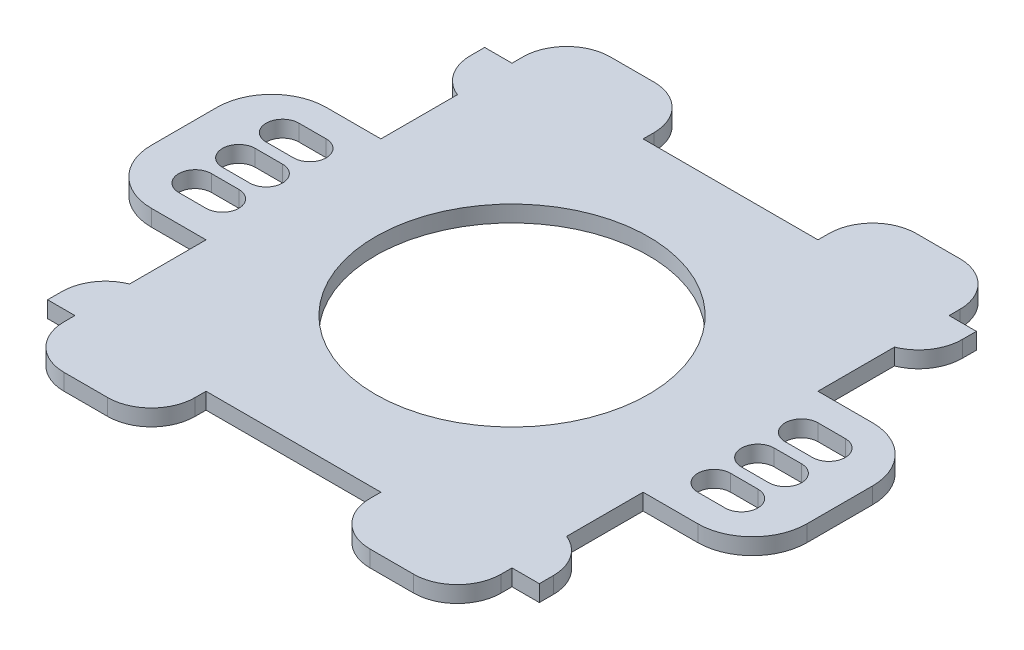
SolidWorks part; units mm, degrees
material "Thornel Mat VMA"
ref_plane "前视基准面" through (0, 0, 0) normal (0, 0, 1) x (1, 0, 0)
ref_plane "上视基准面" through (0, 0, 0) normal (0, 1, 0) x (1, 0, 0)
ref_plane "右视基准面" through (0, 0, 0) normal (1, 0, 0) x (0, 0, -1)
other "Configuration Table"
sketch "草图1" plane through (0, 0, 0) normal (0, 1, 0) x (1, 0, 0)
  line L1 (-20, -25) -> (20, -25)
  line L2 (-20, -25) -> (-20, 25)
  line L3 (-20, 25) -> (20, 25)
  line L4 (20, -25) -> (20, 25)
  line L5 (-20, -25) -> (20, 25) construction
  line L6 (-20, 25) -> (20, -25) construction
  point P0 (0, 0)
  dimension "D1" = 40
  dimension "D2" = 50
extrude "凸台-拉伸1" add sketch "草图1" along normal blind 1.5
sketch "草图3" plane through (0, 1.5, 0) normal (0, 1, 0) x (1, 0, 0)
  line L0 (-1000, 0) -> (49000, 0) construction
  line L1 (-22.5, -20) -> (22.5, -20)
  line L2 (-22.5, -20) -> (-22.5, -15)
  line L3 (-22.5, -15) -> (22.5, -15)
  line L4 (22.5, -20) -> (22.5, -15)
  line L5 (-22.5, -20) -> (22.5, -15) construction
  line L6 (-22.5, -15) -> (22.5, -20) construction
  line L7 (-20, -25) -> (20, -25) construction
  line L8 (-22.5, 15) -> (22.5, 15)
  line L9 (22.5, 20) -> (22.5, 15)
  line L10 (-22.5, 20) -> (22.5, 20)
  line L11 (-22.5, 20) -> (-22.5, 15)
  point P0 (0, -17.5)
  dimension "D1" = 5
  dimension "D2" = 5
  dimension "D3" = 45
  dimension "D4" = 0
extrude "凸台-拉伸2" add sketch "草图3" against normal blind 1.5
sketch "草图4" plane through (0, 1.5, 0) normal (0, 1, 0) x (1, 0, 0)
  line L4 (-30, -8) -> (30, -8)
  line L5 (-30, -8) -> (-30, 8)
  line L6 (-30, 8) -> (30, 8)
  line L7 (30, -8) -> (30, 8)
  line L8 (-30, -8) -> (30, 8) construction
  line L9 (-30, 8) -> (30, -8) construction
  point P0 (0, 0)
  dimension "D4" = 0
  dimension "D1" = 16
  dimension "D2" = 60
  dimension "D3" = 0
extrude "凸台-拉伸3" add sketch "草图4" against normal blind 1.5
sketch "草图6" plane through (0, 1.5, 0) normal (0, 1, 0) x (1, 0, 0)
  line L1 (-25, 0) -> (-22.5, 0) construction
  line L2 (-25, 1.5) -> (-22.5, 1.5)
  line L3 (-25, -1.5) -> (-22.5, -1.5)
  line L4 (-25, 4) -> (-22.5, 4) construction
  line L5 (-25, 5.5) -> (-22.5, 5.5)
  line L6 (-25, 2.5) -> (-22.5, 2.5)
  line L7 (-25, -4) -> (-22.5, -4) construction
  line L8 (-25, -2.5) -> (-22.5, -2.5)
  line L9 (-25, -5.5) -> (-22.5, -5.5)
  line L10 (0, -1000) -> (0, 49000) construction
  line L11 (25, -4) -> (22.5, -4) construction
  line L12 (25, -2.5) -> (22.5, -2.5)
  line L13 (25, -5.5) -> (22.5, -5.5)
  line L14 (25, 0) -> (22.5, 0) construction
  line L15 (25, 1.5) -> (22.5, 1.5)
  line L16 (25, -1.5) -> (22.5, -1.5)
  line L17 (25, 4) -> (22.5, 4) construction
  line L18 (25, 5.5) -> (22.5, 5.5)
  line L19 (25, 2.5) -> (22.5, 2.5)
  arc A3 (-25, 1.5) -> (-25, -1.5) centre (-25, 0) ccw
  arc A4 (-22.5, -1.5) -> (-22.5, 1.5) centre (-22.5, 0) ccw
  arc A5 (-25, 5.5) -> (-25, 2.5) centre (-25, 4) ccw
  arc A6 (-22.5, 2.5) -> (-22.5, 5.5) centre (-22.5, 4) ccw
  arc A7 (-25, -2.5) -> (-25, -5.5) centre (-25, -4) ccw
  arc A8 (-22.5, -5.5) -> (-22.5, -2.5) centre (-22.5, -4) ccw
  arc A9 (25, -2.5) -> (25, -5.5) centre (25, -4) cw
  arc A10 (22.5, -5.5) -> (22.5, -2.5) centre (22.5, -4) cw
  arc A11 (25, 1.5) -> (25, -1.5) centre (25, 0) cw
  arc A12 (22.5, -1.5) -> (22.5, 1.5) centre (22.5, 0) cw
  arc A13 (25, 5.5) -> (25, 2.5) centre (25, 4) cw
  arc A14 (22.5, 2.5) -> (22.5, 5.5) centre (22.5, 4) cw
  point P2 (-23.75, 0)
  point P11 (-23.75, 4)
  point P18 (-23.75, -4)
  point P27 (23.75, -4)
  point P34 (23.75, 0)
  point P41 (23.75, 4)
  dimension "D1" = 25
  dimension "D2" = 22.5
  dimension "D3" = 1.5
extrude "切除-拉伸3" cut sketch "草图6" against normal through all
fillet "圆角1" radius 5 4 edges at (30, 0.75, 8) (30, 0.75, -8) (-30, 0.75, 8) (-30, 0.75, -8)
sketch "草图7" plane through (0, 1.5, 0) normal (0, 1, 0) x (1, 0, 0)
  circle A0 centre (0, 0) radius 12.5
  dimension "D1" = 25
extrude "切除-拉伸4" cut sketch "草图7" against normal through all
sketch "草图9" plane through (0, 1.5, 0) normal (0, 1, 0) x (1, 0, 0)
  line L0 (20, 25) -> (-20, 25) construction
  line L1 (-8, 20) -> (8, 20)
  line L2 (-8, 20) -> (-8, 25)
  line L3 (-8, 25) -> (8, 25)
  line L4 (8, 20) -> (8, 25)
  line L5 (-8, 20) -> (8, 25) construction
  line L6 (-8, 25) -> (8, 20) construction
  line L7 (-1000, 0) -> (49000, 0) construction
  line L8 (-8, -25) -> (8, -25)
  line L9 (8, -20) -> (8, -25)
  line L10 (-8, -20) -> (8, -20)
  line L11 (-8, -20) -> (-8, -25)
  point P0 (0, 22.5)
  dimension "D1" = 0
  dimension "D2" = 16
  dimension "D3" = 5
extrude "切除-拉伸5" cut sketch "草图9" against normal through all
fillet "圆角2" radius 4 12 edges at (-22.5, 0.75, -15) (22.5, 0.75, -15) (22.5, 0.75, 15) (-22.5, 0.75, 15) (-20, 0.75, 25) (20, 0.75, 25) (-20, 0.75, -25) (20, 0.75, -25) (8, 0.75, 25) (-8, 0.75, 25) (8, 0.75, -25) (-8, 0.75, -25)
